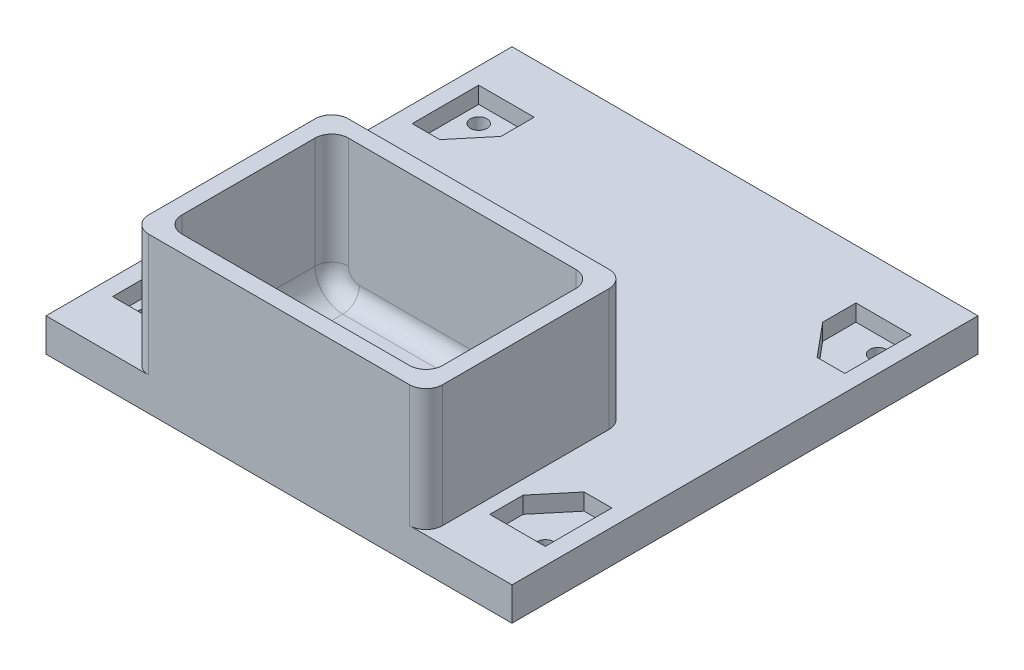
SolidWorks part; units mm, degrees
ref_plane "Front Plane" through (0, 0, 0) normal (0, 0, 1) x (1, 0, 0)
ref_plane "Top Plane" through (0, 0, 0) normal (0, 1, 0) x (1, 0, 0)
ref_plane "Right Plane" through (0, 0, 0) normal (1, 0, 0) x (0, 0, -1)
sketch "Sketch1" plane through (0, 0, 0) normal (0, 1, 0) x (1, 0, 0)
  line L1 (0, 0) -> (84, 0)
  line L2 (0, 0) -> (0, 84)
  line L3 (0, 84) -> (84, 84)
  line L4 (84, 0) -> (84, 84)
  dimension "D1" = 84
  dimension "D2" = 84
extrude "Boss-Extrude1" add sketch "Sketch1" along normal blind 6
sketch "Sketch2" plane through (0, 6, 0) normal (0, 1, 0) x (1, 0, 0)
  line L0 (84, 84) -> (0, 84) construction
  line L1 (0, 84) -> (0, 0) construction
  line L2 (0, 0) -> (84, 0) construction
  line L3 (84, 0) -> (84, 84) construction
  circle A0 centre (6, 72) radius 1.5
  circle A1 centre (6, 12) radius 1.5
  circle A2 centre (78, 12) radius 1.5
  circle A3 centre (78, 72) radius 1.5
  dimension "D1" = 3
  dimension "D2" = 3
  dimension "D3" = 3
  dimension "D4" = 3
  dimension "D6" = 6
  dimension "D7" = 12
  dimension "D8" = 6
  dimension "D9" = 6
  dimension "D10" = 12
  dimension "D11" = 6
  dimension "D5" = 12
  dimension "D12" = 12
extrude "Cut-Extrude1" cut sketch "Sketch2" against normal through all
ref_plane "Plane1" through (0, 0, -42) normal (0, 0, 1) x (1, 0, 0)
sketch "Sketch4" plane through (0, 6, 0) normal (0, 1, 0) x (1, 0, 0)
  line L0 (3, 21) -> (3, 9)
  line L1 (3, 9) -> (13, 9)
  line L2 (13, 15) -> (8, 21)
  line L3 (3, 21) -> (8, 21)
  line L4 (8, 21) -> (13, 15)
  line L5 (13, 15) -> (13, 9)
  line L6 (0, 84) -> (0, 0) construction
  line L7 (0, 0) -> (84, 0) construction
  circle A0 centre (6, 12) radius 1.5
  circle A1 centre (6, 12) radius 1.5 construction
  circle M21 centre (6, 12) radius 1.5
  dimension "D1" = 3
  dimension "D2" = 9
  dimension "D3" = 12
  dimension "D4" = 10
  dimension "D5" = 6
  dimension "D6" = 5
extrude "Cut-Extrude4" cut sketch "Sketch4" against normal blind 3 contours L5 L2 L3 L0 L1 M21 region at (7.6338, 6, -14.6039)
mirror "Mirror2" about plane through (0, 0, -42) normal (0, 0, 1) of "Cut-Extrude4"
ref_plane "Plane2" through (42, 0, 0) normal (-1, 0, 0) x (0, 0, 1)
mirror "Mirror3" about plane through (42, 0, 0) normal (-1, 0, 0) of "Mirror2"
sketch "Sketch5" plane through (0, 6, 0) normal (0, 1, 0) x (1, 0, 0)
  line L0 (15.5, 36) -> (15.5, 0)
  line L1 (15.5, 36) -> (68.5, 36)
  line L2 (15.5, 0) -> (68.5, 0)
  line L3 (68.5, 36) -> (68.5, 0)
  line L4 (15.5, 36) -> (68.5, 0) construction
  line L5 (15.5, 0) -> (68.5, 36) construction
  line L6 (42, 3.3) -> (42, -3.3) construction
  line L12 (0, 0) -> (84, 0) construction
  point P1 (42, 18)
  dimension "D1" = 53
  dimension "D2" = 36
extrude "Boss-Extrude2" add sketch "Sketch5" along normal blind 22
sketch "Sketch6" plane through (0, 28, 0) normal (0, 1, 0) x (1, 0, 0)
  line L14 (65.5, 33) -> (18.5, 33)
  line L15 (18.5, 33) -> (18.5, 3)
  line L16 (18.5, 3) -> (65.5, 3)
  line L17 (65.5, 3) -> (65.5, 33)
  line L18 (65.5, 33) -> (18.5, 33)
  line L19 (18.5, 33) -> (18.5, 3)
  line L20 (18.5, 3) -> (65.5, 3)
  line L21 (65.5, 3) -> (65.5, 33)
  dimension "D1" = 3
extrude "Cut-Extrude5" cut sketch "Sketch6" against normal blind 25
fillet "Fillet1" radius 3 10 edges at (65.5, 15.5, -33) (18.5, 15.5, -33) (65.5, 15.5, -3) (18.5, 15.5, -3) (15.5, 17, -36) (68.5, 17, 0) (68.5, 17, -36) (15.5, 17, 0) (42, 3, -3) (42, 3, -33)
fillet "Fillet2" radius 5 6 edges at (19.3787, 3.8787, -3.8787) (19.3787, 3.8787, -32.1213) (64.6213, 3.8787, -32.1213) (64.6213, 3.8787, -3.8787) (65.5, 3, -18) (18.5, 3, -18)
